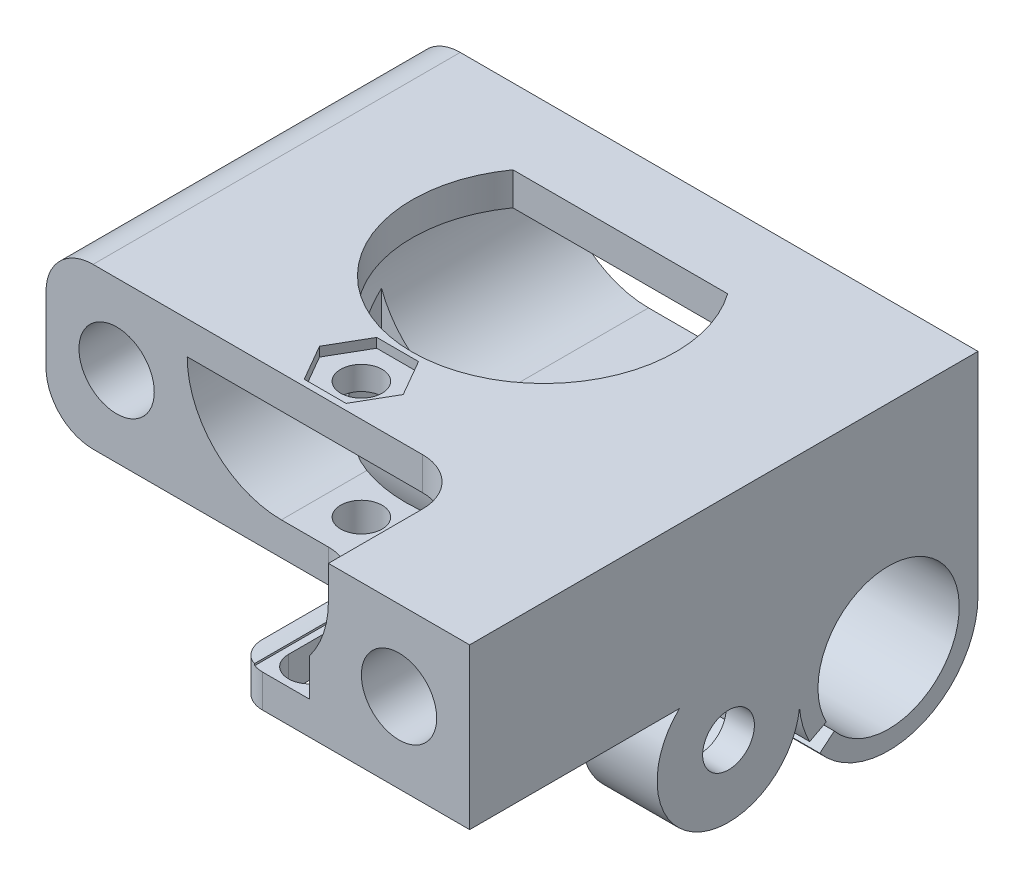
SolidWorks part; units mm, degrees
material "ABS generico"
ref_plane "Front Plane" through (0, 0, 0) normal (0, 0, 1) x (1, 0, 0)
ref_plane "Top Plane" through (0, 0, 0) normal (0, 1, 0) x (1, 0, 0)
ref_plane "Right Plane" through (0, 0, 0) normal (1, 0, 0) x (0, 0, -1)
sketch "Sketch1" plane through (0, 0, 0) normal (1, 0, 0) x (0, 0, -1)
  line L1 (21.1236, -26.9641) -> (22.8813, -26.0274)
  line L3 (23.7305, -27.2923) -> (22.1984, -28.5649)
  line L4 (20.0416, -23.294) -> (20.0416, -17)
  line L8 (39, 0) -> (0, 0)
  line L12 (0, -17) -> (0, 0)
  line L13 (0, -17) -> (20.0416, -17)
  line L15 (39, -22.5) -> (39, 0)
  line L19 (16.5, -29.4282) -> (20.0416, -23.294) construction
  line L20 (8.5, -29.4282) -> (16.5, -29.4282) construction
  line L21 (4.5, -22.5) -> (8.5, -29.4282) construction
  line L22 (4.5, -17) -> (4.5, -22.5) construction
  arc A0 (23.7305, -27.2923) -> (22.8813, -26.0274) centre (29.5041, -22.4988) ccw
  arc A1 (20.0416, -23.294) -> (21.1236, -26.9641) centre (29.5041, -22.4988) ccw
  arc A2 (22.1984, -28.5649) -> (39, -22.5) centre (29.5041, -22.4988) ccw
  circle A5 centre (12.5, -22.5) radius 2.75 construction
  dimension "D2" = 7.5042
  dimension "D3" = 9.4959
  dimension "D1" = 39
  dimension "D4" = 17
extrude "Extrude1" add sketch "Sketch1" against normal blind 60
sketch "Sketch2" plane through (0, 0, 0) normal (0, 0, 1) x (1, 0, 0)
  line L0 (-60, -8.5) -> (0, -8.5) construction
  line L1 (-60, 0) -> (-60, -17) construction
  line L2 (0, 0) -> (0, -17) construction
  line L3 (-30, 1.8171) -> (-30, -40.9837) construction
  line L5 (-15, -13.5) -> (-45, -13.5)
  line L6 (-15, -13.5) -> (-15, -3.5)
  line L7 (-15, -3.5) -> (-45, -3.5)
  line L8 (-45, -13.5) -> (-45, -3.5)
  line L9 (-15, -13.5) -> (-45, -3.5) construction
  line L10 (-15, -3.5) -> (-45, -13.5) construction
  circle A0 centre (-52.5, -8.5) radius 4
  circle A1 centre (-7.5, -8.5) radius 4
  point P12 (-30, -8.5)
  dimension "D1" = 8
  dimension "D2" = 22.5
  dimension "D3" = 7.5
  dimension "D4" = 10
  dimension "D5" = 30
extrude "Extrude2" cut sketch "Sketch2" against normal up to surface (39 mm away) up to face at (-30, -11.25, -39)
sketch "Sketch3" plane through (0, 0, 0) normal (0, 0, 1) x (1, 0, 0)
  line L0 (-52.5, -8.5) -> (-7.5, -8.5) construction
  line L1 (-52.5, -8.5) -> (-52.5, 8.8734) construction
  line L2 (-32.5, -8.5) -> (-32.5, 8.8734) construction
  dimension "D1" = 20
sketch "Sketch4" plane through (0, 0, 0) normal (1, 0, 0) x (0, 0, -1)
  line L0 (7.2804, -17) -> (20.0416, -17)
  line L1 (12.5, -17.9967) -> (8.6, -20.2483) construction
  line L2 (8.6, -20.2483) -> (8.6, -24.7517) construction
  line L3 (8.6, -24.7517) -> (12.5, -27.0033) construction
  line L4 (12.5, -27.0033) -> (16.4, -24.7517) construction
  line L5 (16.4, -24.7517) -> (16.4, -20.2483) construction
  line L6 (16.4, -20.2483) -> (12.5, -17.9967) construction
  line L7 (0, -17) -> (20.0416, -17) construction
  line L8 (20.0416, -17) -> (20.0817, -22.3872)
  circle A0 centre (12.5, -22.5) radius 3.9 construction
  arc A1 (7.2804, -17) -> (20.0817, -22.3872) centre (12.5, -22.5) ccw
  dimension "D1" = 7.8
extrude "Extrude3" add sketch "Sketch4" against normal blind 8
sketch "Sketch5" plane through (0, 0, 0) normal (1, 0, 0) x (0, 0, -1)
  circle A0 centre (12.5, -22.5) radius 2.75
  dimension "D1" = 5.5
extrude "Extrude4" cut sketch "Sketch5" against normal up to surface (8 mm away) up to face at (-8, -22.1484, -14.2839)
sketch "Sketch6" plane through (-8, 0, 0) normal (-1, 0, 0) x (0, 0, 1)
  line L1 (-12.5, -17.8812) -> (-16.5, -20.1906)
  line L2 (-16.5, -20.1906) -> (-16.5, -24.8094)
  line L3 (-16.5, -24.8094) -> (-12.5, -27.1188)
  line L4 (-12.5, -27.1188) -> (-8.5, -24.8094)
  line L5 (-8.5, -24.8094) -> (-8.5, -20.1906)
  line L6 (-8.5, -20.1906) -> (-12.5, -17.8812)
extrude "Extrude5" cut sketch "Sketch6" against normal blind 5
sketch "Sketch7" plane through (0, 0, 0) normal (0, 1, 0) x (1, 0, 0)
  line L2 (-31, -370.8295) -> (-31, 97.9462) construction
  line L6 (-30.9897, -180.6724) -> (-30.9897, -405.4164) construction
  circle A0 centre (-31, 4.5) radius 2.2
extrude "Extrude6" cut sketch "Sketch7" against normal up to surface (17 mm away) up to face at (-22.6667, -17, -9.1073)
sketch "Sketch8" plane through (0, 0, -39) normal (0, 0, -1) x (-1, 0, 0)
  line L0 (7.5, -8.5) -> (52.5, -8.5) construction
  line L1 (30, -8.5) -> (30, 3.0319) construction
  circle A0 centre (7.5, -8.5) radius 4.201
  circle A1 centre (52.5, -8.5) radius 1.25
  circle A2 centre (7.5, -8.5) radius 1.25
  circle A3 centre (52.5, -8.5) radius 4.201
  dimension "D1" = 2.5
extrude "Extrude7" add sketch "Sketch8" against normal blind 9
sketch "Sketch10" plane through (-60, 0, 0) normal (-1, 0, 0) x (0, 0, 1)
  line L1 (-20.0416, -17) -> (-39.247, -17)
  line L2 (-20.0416, -17) -> (-20.0416, -32.1139)
  line L3 (-20.0416, -32.1139) -> (-39.247, -32.1139)
  line L4 (-39.247, -17) -> (-39.247, -32.1139)
extrude "Extrude8" cut sketch "Sketch10" against normal blind 10
fillet "Fillet9" radius 10 2 edges at (-55, -17, -24.3976) (-55, -17, -34.6107)
fillet "Fillet11" radius 5 1 edges at (-60, 0, -19.5)
fillet "Fillet12" radius 5 5 edges at (-60, -17, -38.3198) (-60, -16.7094, -35.2462) (-60, -14.9946, -29.5041) (-60, -16.7094, -23.7621) (-60, -17, -10.6843)
sketch "Sketch12" plane through (0, 0, 0) normal (0, 0, 1) x (1, 0, 0)
  line L0 (-15, -13.5) -> (-15, 2.5343) construction
  line L1 (0, 0) -> (-20.7492, 0) construction
  line L2 (-55, 0) -> (0, 0) construction
  line L3 (-45, -13.5) -> (-15, -13.5) construction
  line L4 (-15, 0) -> (0, 0)
  line L5 (-11.5, -8.5) -> (-11.5, 2.5343) construction
  line L6 (-15, -17) -> (0, -17)
  line L7 (0, 0) -> (0, -17)
  line L8 (-15, -17) -> (-25, -17)
  line L9 (-25, -13.5) -> (-15, -13.5)
  line L10 (-15, -13.5) -> (-15, 0)
  line L11 (-25, -17) -> (-25, -13.5)
  circle A0 centre (-7.5, -8.5) radius 4
  point P21 (-14.5, -8.5)
  point P22 (-14.5, 2.5343)
  dimension "D3" = 8
  dimension "D1" = 10
extrude "Extrude10" add sketch "Sketch12" along normal blind 15
sketch "Sketch13" plane through (0, -17, 0) normal (0, -1, 0) x (1, 0, 0)
  line L0 (0, 10.5645) -> (0, 23.7024) construction
  line L1 (0, 15) -> (0, -7.2804) construction
  line L2 (-20, -5.2455) -> (-20, 23.7024) construction
  line L3 (-20, 10.5645) -> (-20, 23.7024) construction
  line L4 (-25, 0) -> (-9.3359, 0) construction
  line L5 (-25, 15) -> (-25, 0) construction
  line L6 (-20, 12) -> (-20, -3) construction
  line L7 (-17.75, 12) -> (-17.75, -3)
  line L8 (-22.25, 12) -> (-22.25, -3)
  line L9 (-25, 15) -> (0, 15) construction
  arc A0 (-17.75, 12) -> (-22.25, 12) centre (-20, 12) ccw
  arc A1 (-22.25, -3) -> (-17.75, -3) centre (-20, -3) ccw
  point P14 (-20, 4.5)
  dimension "D2" = 3
  dimension "D1" = 5
extrude "Extrude11" cut sketch "Sketch13" against normal up to surface (3.5 mm away) up to face at (-28.8, -13.5, -4.5)
sketch "Sketch14" plane through (0, -17, 0) normal (0, -1, 0) x (1, 0, 0)
  line L1 (-12, -10.2024) -> (-12, 22.3262) construction
  line L3 (-10.5, -3) -> (-10.5, 12)
  line L4 (-13.5, 12) -> (-13.5, -3)
  arc A2 (-10.5, 12) -> (-13.5, 12) centre (-12, 12) ccw
  arc A3 (-13.5, -3) -> (-10.5, -3) centre (-12, -3) ccw
extrude "Extrude12" cut sketch "Sketch14" against normal blind 2
chamfer "Chamfer1" distance 1 angle 45 4 edges at (-13.5, -17, 4.5) (-12, -17, -4.5) (-12, -17, 13.5) (-10.5, -17, 4.5)
fillet "Fillet15" radius 3 1 edges at (-25, -15.25, 15)
sketch "Sketch15" plane through (0, 0, 0) normal (0, 1, 0) x (1, 0, 0)
  line L0 (-50, 22.8813) -> (0, 22.8813) construction
  line L1 (-41.4058, 31) -> (-18.5942, 31)
  arc A0 (-41.4058, 31) -> (-18.5942, 31) centre (-30, 22.8813) ccw
extrude "Extrude13" cut sketch "Sketch15" against normal blind 9
fillet "Fillet18" radius 1 4 edges at (-13.5, -15, 4.5) (-12, -15, 13.5) (-10.5, -15, 4.5) (-12, -15, -4.5)
fillet "Fillet19" radius 11 4 edges at (-13.5, -16, 4.5) (-12, -16, 13.5) (-10.5, -16, 4.5) (-12, -16, -4.5)
fillet "Fillet20" radius 10 1 edges at (-45, -13.5, -19.5)
sketch "Sketch16" plane through (0, -17, 0) normal (0, -1, 0) x (1, 0, 0)
  line L0 (-30, -8.881) -> (-30, -22.8813) construction
  line L1 (-44.4017, -20.0416) -> (-15.5983, -20.0416)
  arc A1 (-15.5983, -20.0416) -> (-44.4017, -20.0416) centre (-30, -22.8813) ccw
extrude "Extrude14" cut sketch "Sketch16" against normal up to surface (13.5 mm away) up to face at (-30, -3.5, -19.9405)
fillet "Fillet21" radius 10 1 edges at (-15, -13.5, -12)
fillet "Fillet22" radius 5 1 edges
fillet "Fillet23" radius 5 1 edges
sketch "Sketch17" plane through (0, 0, 0) normal (0, 1, 0) x (1, 0, 0)
  line L7 (-35.4444, 4.5) -> (-33.2222, 0.651)
  line L8 (-33.2222, 0.651) -> (-28.7778, 0.651)
  line L9 (-28.7778, 0.651) -> (-26.5556, 4.5)
  line L10 (-26.5556, 4.5) -> (-28.7778, 8.349)
  line L11 (-28.7778, 8.349) -> (-33.2222, 8.349)
  line L12 (-33.2222, 8.349) -> (-35.4444, 4.5)
  circle A0 centre (-31, 4.5) radius 3.849 construction
extrude "Cut-Extrude1" cut sketch "Sketch17" against normal blind 1
sketch "Sketch18" plane through (0, -3.5, 0) normal (0, -1, 0) x (1, 0, 0)
  line L0 (-20, -5.25) -> (-20, 17.0853) construction
  line L1 (-17, -3) -> (-17, 17.0853)
  line L2 (-23, -3) -> (-23, 17.0853)
  line L3 (-16.6454, -3) -> (-23.5438, -3) construction
  line L4 (-23, 17.0853) -> (-17, 17.0853)
  line L5 (-23, -5.25) -> (-23, 17.0853) construction
  line L6 (-17, -5.25) -> (-17, 17.0853) construction
  arc A0 (-22.25, -3) -> (-17.75, -3) centre (-20, -3) ccw construction
  arc A1 (-23, -3) -> (-17, -3) centre (-20, -3) ccw
  dimension "D1" = 3
  dimension "D2" = 3
extrude "Cut-Extrude2" cut sketch "Sketch18" along normal up to surface (10 mm away) up to face at (-30, -13.5, -29.5208)
